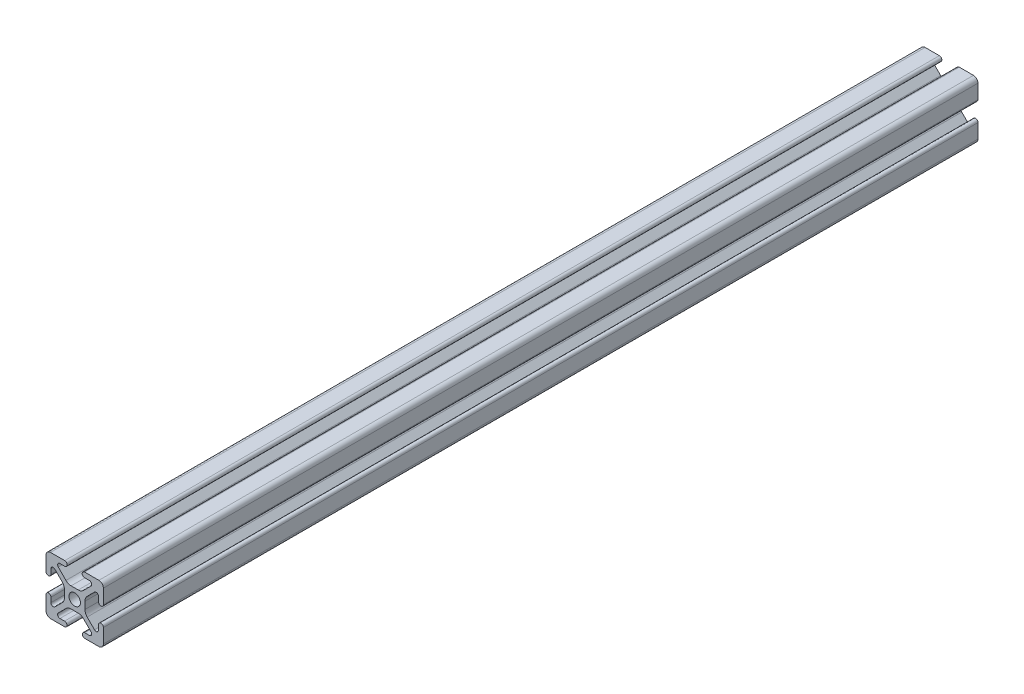
SolidWorks part; units mm, degrees
ref_plane "Front" through (0, 0, 0) normal (0, 0, 1) x (1, 0, 0)
ref_plane "Top" through (0, 0, 0) normal (0, 1, 0) x (1, 0, 0)
ref_plane "Right" through (0, 0, 0) normal (1, 0, 0) x (0, 0, -1)
ref_plane "Plane1" through (0, 0, -381) normal (0, 0, -1) x (-1, 0, 0)
sketch "Sketch1" plane through (0, 0, -381) normal (0, 0, -1) x (-1, 0, 0)
  line L0 (12.5, 4.32) -> (12.5, 10.5371)
  line L1 (10.5371, 12.5) -> (4.32, 12.5)
  line L2 (4.32, 10.36) -> (6.42, 10.36)
  line L3 (7.1337, 8.6353) -> (3.7953, 5.3018)
  line L4 (1.5554, 4.375) -> (-1.5554, 4.375)
  line L5 (-3.7953, 5.3018) -> (-7.1337, 8.6353)
  line L6 (-6.42, 10.36) -> (-4.32, 10.36)
  line L7 (-4.32, 12.5) -> (-10.5371, 12.5)
  line L8 (-12.5, 10.5371) -> (-12.5, 4.32)
  line L9 (-10.36, 4.32) -> (-10.36, 6.3969)
  line L10 (-8.6363, 7.1116) -> (-5.4322, 3.9121)
  line L11 (-4.455, 1.5554) -> (-4.455, -1.5554)
  line L12 (-5.4322, -3.9121) -> (-8.6363, -7.1116)
  line L13 (-10.36, -6.3969) -> (-10.36, -4.32)
  line L14 (-12.5, -4.32) -> (-12.5, -10.5371)
  line L15 (-10.5371, -12.5) -> (-4.3879, -12.5)
  line L16 (-4.3879, -10.36) -> (-6.42, -10.36)
  line L17 (-7.1337, -8.6353) -> (-3.7953, -5.3018)
  line L18 (-1.5554, -4.375) -> (1.5554, -4.375)
  line L19 (3.7953, -5.3018) -> (7.1337, -8.6353)
  line L20 (6.42, -10.36) -> (4.3879, -10.36)
  line L21 (4.3879, -12.5) -> (10.5371, -12.5)
  line L22 (12.5, -10.5371) -> (12.5, -4.32)
  line L23 (10.36, -4.32) -> (10.36, -6.3969)
  line L24 (8.6363, -7.1116) -> (5.4322, -3.9121)
  line L25 (4.455, -1.5554) -> (4.455, 1.5554)
  line L26 (5.4322, 3.9121) -> (8.6363, 7.1116)
  line L27 (10.36, 6.3969) -> (10.36, 4.32)
  circle A0 centre (0, 0) radius 2.5
  arc A1 (12.5, 10.5371) -> (10.5371, 12.5) centre (10.5371, 10.5371) ccw
  arc A2 (4.32, 12.5) -> (4.32, 10.36) centre (4.32, 11.43) ccw
  arc A3 (6.42, 10.36) -> (7.1337, 8.6353) centre (6.42, 9.35) cw
  arc A4 (3.7953, 5.3018) -> (1.5554, 4.375) centre (1.5554, 7.545) cw
  arc A5 (-1.5554, 4.375) -> (-3.7953, 5.3018) centre (-1.5554, 7.545) cw
  arc A6 (-7.1337, 8.6353) -> (-6.42, 10.36) centre (-6.42, 9.35) cw
  arc A7 (-4.32, 10.36) -> (-4.32, 12.5) centre (-4.32, 11.43) ccw
  arc A8 (-10.5371, 12.5) -> (-12.5, 10.5371) centre (-10.5371, 10.5371) ccw
  arc A9 (-12.5, 4.32) -> (-10.36, 4.32) centre (-11.43, 4.32) ccw
  arc A10 (-10.36, 6.3969) -> (-8.6363, 7.1116) centre (-9.35, 6.3969) cw
  arc A11 (-5.4322, 3.9121) -> (-4.455, 1.5554) centre (-7.7855, 1.5554) cw
  arc A12 (-4.455, -1.5554) -> (-5.4322, -3.9121) centre (-7.7855, -1.5554) cw
  arc A13 (-8.6363, -7.1116) -> (-10.36, -6.3969) centre (-9.35, -6.3969) cw
  arc A14 (-10.36, -4.32) -> (-12.5, -4.32) centre (-11.43, -4.32) ccw
  arc A15 (-12.5, -10.5371) -> (-10.5371, -12.5) centre (-10.5371, -10.5371) ccw
  arc A16 (-4.3879, -12.5) -> (-4.3879, -10.36) centre (-4.3879, -11.43) ccw
  arc A17 (-6.42, -10.36) -> (-7.1337, -8.6353) centre (-6.42, -9.35) cw
  arc A18 (-3.7953, -5.3018) -> (-1.5554, -4.375) centre (-1.5554, -7.545) cw
  arc A19 (1.5554, -4.375) -> (3.7953, -5.3018) centre (1.5554, -7.545) cw
  arc A20 (7.1337, -8.6353) -> (6.42, -10.36) centre (6.42, -9.35) cw
  arc A21 (4.3879, -10.36) -> (4.3879, -12.5) centre (4.3879, -11.43) ccw
  arc A22 (10.5371, -12.5) -> (12.5, -10.5371) centre (10.5371, -10.5371) ccw
  arc A23 (12.5, -4.32) -> (10.36, -4.32) centre (11.43, -4.32) ccw
  arc A24 (10.36, -6.3969) -> (8.6363, -7.1116) centre (9.35, -6.3969) cw
  arc A25 (5.4322, -3.9121) -> (4.455, -1.5554) centre (7.7855, -1.5554) cw
  arc A26 (4.455, 1.5554) -> (5.4322, 3.9121) centre (7.7855, 1.5554) cw
  arc A27 (8.6363, 7.1116) -> (10.36, 6.3969) centre (9.35, 6.3969) cw
  arc A28 (10.36, 4.32) -> (12.5, 4.32) centre (11.43, 4.32) ccw
  point P86 (0, 0)
  point P87 (0, 0)
  dimension "D1" = 5
  dimension "D2" = 1.9629
  dimension "D3" = 1.07
  dimension "D4" = 1.01
  dimension "D5" = 3.17
  dimension "D6" = 3.3305
  dimension "D7" = 1.5554
  dimension "D8" = 3.7953
  dimension "D9" = 4.32
  dimension "D10" = 4.3879
  dimension "D11" = 4.455
  dimension "D12" = 1.5554
  dimension "D13" = 11.43
  dimension "D14" = 11.43
extrude "Boss-Extrude1" add sketch "Sketch1" against normal blind 381
